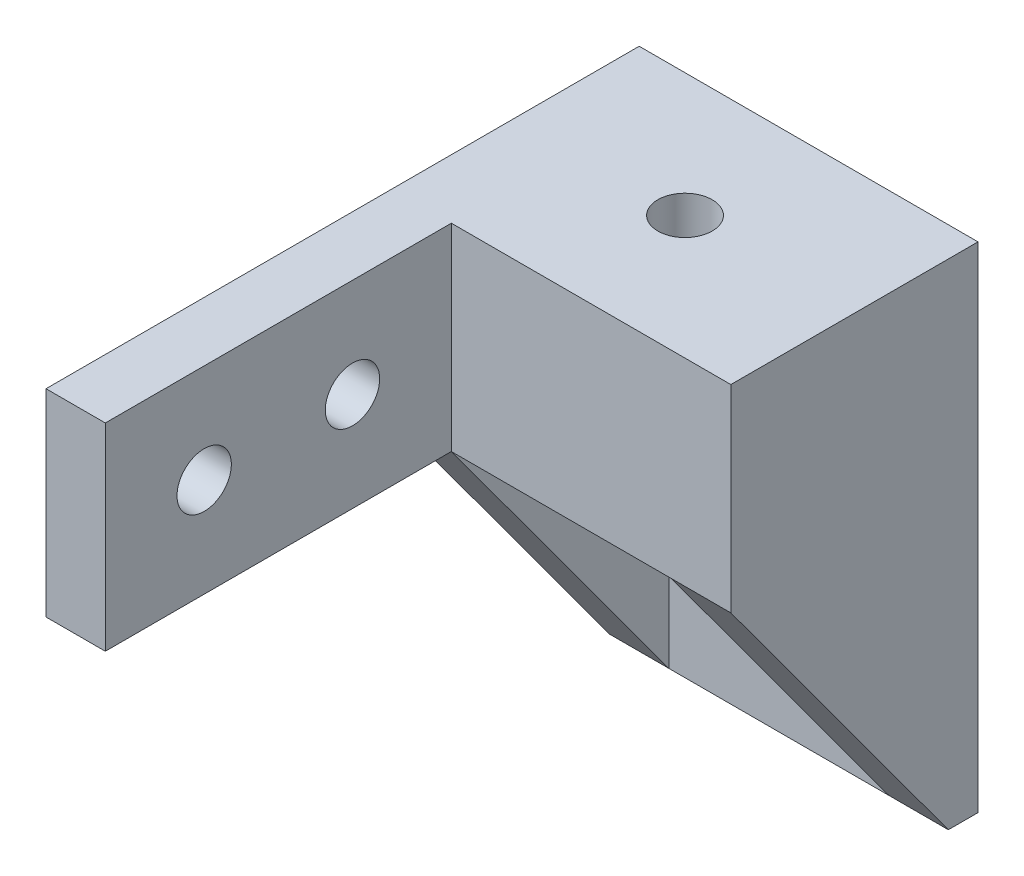
SolidWorks part; units mm, degrees
ref_plane "Front" through (0, 0, 0) normal (0, 0, 1) x (1, 0, 0)
ref_plane "Top" through (0, 0, 0) normal (0, 1, 0) x (1, 0, 0)
ref_plane "Right" through (0, 0, 0) normal (1, 0, 0) x (0, 0, -1)
sketch "Sketch1" plane through (0, 0, 0) normal (0, 1, 0) x (1, 0, 0)
  line L1 (0, 0) -> (17.135, 0)
  line L2 (0, 0) -> (0, 12.5)
  line L3 (0, 12.5) -> (17.135, 12.5)
  line L4 (17.135, 0) -> (17.135, 12.5)
  dimension "D1" = 17.135
  dimension "D2" = 12.5
extrude "base" add sketch "Sketch1" along normal blind 5
sketch "Sketch2" plane through (0, 0, -12.5) normal (0, 0, -1) x (-1, 0, 0)
  line L0 (0, 5) -> (0, 0) construction
  line L1 (-17.135, 0) -> (0, 0)
  line L2 (-17.135, 0) -> (-17.135, -15)
  line L3 (-17.135, -15) -> (0, -15)
  line L4 (0, 0) -> (0, -15)
  dimension "D1" = 15
extrude "Boss-Extrude2" add sketch "Sketch2" against normal blind 1.5
sketch "Sketch3" plane through (0, 0, 0) normal (-1, 0, 0) x (0, 0, 1)
  line L0 (0, 0) -> (-11, -15)
  line L1 (-11, -15) -> (-11, 0)
  line L2 (-11, 0) -> (0, 0)
extrude "Boss-Extrude3" add sketch "Sketch3" against normal up to surface (17.135 mm away) up to face at (17.135, -3.3333, -7.8333)
sketch "Sketch4" plane through (0, 0, 0) normal (0, 0, 1) x (1, 0, 0)
  line L0 (17.135, -15) -> (0, -15) construction
  line L1 (3, 0) -> (14.135, 0)
  line L2 (3, 0) -> (3, -15)
  line L3 (3, -15) -> (14.135, -15)
  line L4 (14.135, 0) -> (14.135, -15)
  line L5 (0, 0) -> (17.135, 0) construction
  line L6 (17.135, 0) -> (17.135, -15) construction
  point P6 (8.5675, 0)
  point P9 (8.5675, 0)
  dimension "D1" = 3
extrude "Cut-Extrude1" cut sketch "Sketch4" against normal up to vertex (11 mm away) up to point (17.135, -15, -11)
sketch "Sketch5" plane through (0, 0, -11) normal (0, 0, 1) x (1, 0, 0)
  line L0 (14.135, 0) -> (3, 0) construction
  line L1 (3, -15) -> (14.135, -15) construction
  circle A0 centre (8.5675, -4) radius 2.3 construction
  circle A1 centre (8.5675, -11) radius 2.3 construction
  circle A2 centre (8.5675, -4) radius 1.375
  circle A3 centre (8.5675, -11) radius 1.375
  point P8 (8.5675, 0)
  dimension "D1" = 4.6
  dimension "D4" = 2.75
  dimension "D2" = 4
  dimension "D3" = 4
extrude "Cut-Extrude2" cut sketch "Sketch5" against normal blind 2
sketch "Sketch6" plane through (0, 5, 0) normal (0, 1, 0) x (1, 0, 0)
  line L0 (0, 12.5) -> (0, 0) construction
  line L1 (0, 0) -> (17.135, 0) construction
  circle A0 centre (8.5675, 6.25) radius 1.375
  dimension "D1" = 2.75
  dimension "D2" = 8.5675
  dimension "D3" = 6.25
extrude "Cut-Extrude3" cut sketch "Sketch6" against normal blind 5.75
sketch "Sketch7" plane through (0, 5, 0) normal (0, 1, 0) x (1, 0, 0)
  line L8 (0, 12.5) -> (0, 0)
  line L9 (0, 0) -> (17.135, 0)
  line L10 (17.135, 0) -> (17.135, 12.5)
  line L11 (17.135, 12.5) -> (0, 12.5)
  line L12 (0, 12.5) -> (0, 0)
  line L13 (0, 0) -> (17.135, 0)
  line L14 (17.135, 0) -> (17.135, 12.5)
  line L15 (17.135, 12.5) -> (0, 12.5)
  circle A0 centre (8.5675, 6.25) radius 1.375 construction
  circle A1 centre (8.5675, 6.25) radius 1.375
  dimension "D1" = 0
extrude "Boss-Extrude4" add sketch "Sketch7" along normal blind 5
sketch "Sketch8" plane through (17.135, 0, 0) normal (1, 0, 0) x (0, 0, -1)
  line L1 (0, 10) -> (-17.5, 10)
  line L2 (0, 10) -> (0, 0)
  line L3 (0, 0) -> (-17.5, 0)
  line L4 (-17.5, 10) -> (-17.5, 0)
  line L5 (-8, 5) -> (-6.5, 2.4019) construction
  line L6 (-6.5, 2.4019) -> (-3.5, 2.4019) construction
  line L7 (-3.5, 2.4019) -> (-2, 5) construction
  line L8 (-2, 5) -> (-3.5, 7.5981) construction
  line L9 (-3.5, 7.5981) -> (-6.5, 7.5981) construction
  line L10 (-6.5, 7.5981) -> (-8, 5) construction
  line L11 (-15.5, 5) -> (-14, 2.4019) construction
  line L12 (-14, 2.4019) -> (-11, 2.4019) construction
  line L13 (-11, 2.4019) -> (-9.5, 5) construction
  line L14 (-9.5, 5) -> (-11, 7.5981) construction
  line L15 (-11, 7.5981) -> (-14, 7.5981) construction
  line L16 (-14, 7.5981) -> (-15.5, 5) construction
  circle A0 centre (-5, 5) radius 1.375
  circle A1 centre (-5, 5) radius 2.5981 construction
  circle A2 centre (-12.5, 5) radius 1.375
  circle A3 centre (-12.5, 5) radius 2.5981 construction
  point P16 (0, 5)
  dimension "D1" = 2.75
  dimension "D2" = 3
  dimension "D3" = 5
  dimension "D4" = 7.5
  dimension "D5" = 5
extrude "Boss-Extrude5" add sketch "Sketch8" against normal blind 3
ref_plane "Plane1" through (8.5675, 0, 0) normal (-1, 0, 0) x (0, 0, 1)
mirror "Mirror1" about plane through (8.5675, 0, 0) normal (-1, 0, 0) of "Boss-Extrude5"
sketch "Sketch9" plane through (14.135, 0, 0) normal (-1, 0, 0) x (0, 0, 1)
  line L4 (0, 10) -> (0, 0)
  line L5 (0, 0) -> (17.5, 0)
  line L6 (17.5, 0) -> (17.5, 10)
  line L7 (17.5, 10) -> (0, 10)
  line L8 (0, 10) -> (0, 0)
  line L9 (0, 0) -> (17.5, 0)
  line L10 (17.5, 0) -> (17.5, 10)
  line L11 (17.5, 10) -> (0, 10)
  dimension "D1" = 0
extrude "Cut-Extrude4" cut sketch "Sketch9" against normal blind 10
